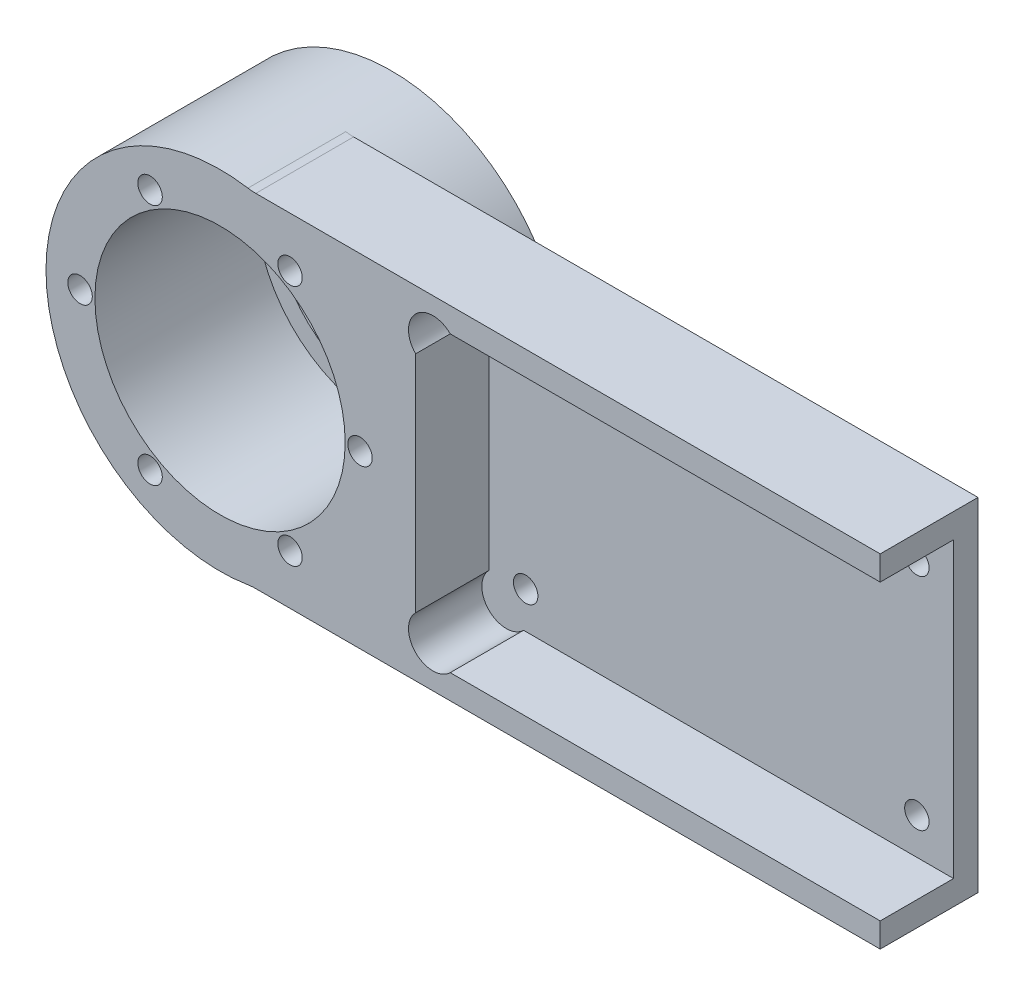
SolidWorks part; units mm, degrees
material "1060 Alloy"
ref_plane "Front Plane" through (0, 0, 0) normal (0, 0, 1) x (1, 0, 0)
ref_plane "Top Plane" through (0, 0, 0) normal (0, 1, 0) x (1, 0, 0)
ref_plane "Right Plane" through (0, 0, 0) normal (1, 0, 0) x (0, 0, -1)
sketch "Sketch1" plane through (0, 0, 0) normal (0, 0, 1) x (1, 0, 0)
  line L0 (8.1998, 44.45) -> (171.45, 44.45)
  line L1 (8.1998, -44.45) -> (171.45, -44.45)
  line L3 (171.45, 44.45) -> (171.45, 38.1)
  line L4 (171.45, -44.45) -> (171.45, -38.1)
  line L5 (171.45, 44.45) -> (171.45, -44.45) construction
  line L6 (171.45, 38.1) -> (50.8, 38.1)
  line L7 (50.8, 38.1) -> (50.8, -38.1)
  line L8 (50.8, -38.1) -> (171.45, -38.1)
  line L9 (171.45, 38.1) -> (171.45, -38.1)
  circle A0 centre (0, 0) radius 32.5
  arc A1 (8.1998, 44.45) -> (8.1998, -44.45) centre (0, 0) ccw
  point P3 (171.45, 0)
  dimension "D1" = 65
  dimension "D4" = 12.7
  dimension "D6" = 50.8
  dimension "D2" = 88.9
  dimension "D3" = 120.65
  dimension "D5" = 6.35
extrude "Boss-Extrude2" add sketch "Sketch1" along normal blind 6.35 contours L0 A1 L1 L4 L8 L7 L6 L3 A0 | L9 L6 L7 L8 region at (37.5693, 0, 0) region at (111.125, 0, 0)
extrude "Boss-Extrude3" add sketch "Sketch1<3>" along normal blind 19.05 from surface contours L0 A1 L1 L4 L8 L7 L6 L3 A0 region at (37.5693, 0, 0) starting at face at (76.475, 0, 6.35)
sketch "Sketch1<3>" plane through (0, 0, 0) normal (0, 0, 1) x (1, 0, 0) same geometry as "Sketch1"
sketch "Sketch2" plane through (0, 0, 6.35) normal (0, 0, 1) x (1, 0, 0)
  line L0 (171.45, -38.1) -> (171.45, 38.1) construction
  line L1 (50.8, -38.1) -> (50.8, 38.1) construction
  line L4 (50.8, 38.1) -> (171.45, 38.1) construction
  line L5 (50.8, 38.1) -> (171.45, 38.1) construction
  line L6 (171.45, -38.1) -> (50.8, -38.1) construction
  line L7 (171.45, -38.1) -> (50.8, -38.1) construction
  circle A0 centre (60.325, 28.575) radius 3.175
  circle A1 centre (161.925, 28.575) radius 3.175
  circle A2 centre (161.925, -28.575) radius 3.175
  circle A3 centre (60.325, -28.575) radius 3.175
  circle A15 centre (0, 0) radius 38.85 construction
  arc A16 (8.1998, 44.45) -> (8.1998, -44.45) centre (0, 0) ccw construction
  dimension "D1" = 6.35
  dimension "D2" = 6.35
  dimension "D4" = 9.525
  dimension "D5" = 9.525
  dimension "D6" = 9.525
  dimension "D3" = 9.525
  dimension "D7" = 9.525
  dimension "D8" = 9.525
extrude "Cut-Extrude1" cut sketch "Sketch2" against normal through all and the other way through all
sketch "Sketch3" plane through (0, 0, 25.4) normal (0, 0, 1) x (1, 0, 0)
  line L0 (50.8, 38.1) -> (59.7803, 29.1197) construction
  line L1 (50.8, 38.1) -> (171.45, 38.1) construction
  line L2 (50.8, 0) -> (32.5, 0) construction
  line L3 (50.8, -38.1) -> (50.8, 38.1) construction
  circle A0 centre (55.2901, 33.6099) radius 6.35
  circle A1 centre (0, 0) radius 32.5 construction
  circle A2 centre (55.2901, -33.6099) radius 6.35
  dimension "D1" = 12.7
  dimension "D2" = 45
extrude "Cut-Extrude2" cut sketch "Sketch3" against normal up to surface (19.05 mm away) up to face at (63.5, -28.575, 6.35)
sketch "Sketch4" plane through (0, 0, 0) normal (0, 0, -1) x (-1, 0, 0)
  line L0 (-31.75, 54.9926) -> (0, 0) construction
  line L1 (0, 0) -> (31.75, 54.9926) construction
  line L2 (-8.1998, -44.45) -> (-171.45, -44.45) construction
  line L3 (0, 0) -> (63.5, 0) construction
  line L4 (0, 0) -> (31.75, -54.9926) construction
  line L9 (-40.7836, 44.45) -> (-8.1998, 44.45)
  line L10 (-8.1998, 44.45) -> (-171.45, 44.45) construction
  line L11 (-8.1998, -44.45) -> (-40.7836, -44.45)
  line L12 (0, 0) -> (-63.5, 0) construction
  line L13 (0, 0) -> (-31.75, -54.9926) construction
  arc A1 (-40.8506, -48.6156) -> (-40.8506, 48.6156) centre (0, 0) ccw construction
  arc A2 (-20.7603, 56.6402) -> (-38.6717, 46.2991) centre (-31.75, 54.9926) ccw
  arc A8 (38.6717, 46.2991) -> (20.7603, 56.6402) centre (31.75, 54.9926) ccw
  arc A9 (59.432, -10.3411) -> (59.432, 10.3411) centre (63.5, 0) ccw
  arc A10 (20.7603, -56.6402) -> (38.6717, -46.2991) centre (31.75, -54.9926) ccw
  arc A11 (-38.6717, -46.2991) -> (-20.7603, -56.6402) centre (-31.75, -54.9926) ccw
  circle A13 centre (-31.75, 54.9926) radius 4.7625
  arc A14 (-38.6717, 46.2991) -> (-40.7836, 44.45) centre (0, 0) ccw
  circle A15 centre (31.75, 54.9926) radius 4.7625
  arc A16 (-8.1998, -44.45) -> (-8.1998, 44.45) centre (0, 0) ccw construction
  arc A17 (20.7603, 56.6402) -> (-20.7603, 56.6402) centre (0, 0) ccw
  circle A18 centre (63.5, 0) radius 4.7625
  circle A19 centre (31.75, -54.9926) radius 4.7625
  arc A20 (59.432, 10.3411) -> (38.6717, 46.2991) centre (0, 0) ccw
  arc A21 (38.6717, -46.2991) -> (59.432, -10.3411) centre (0, 0) ccw
  circle A22 centre (-31.75, -54.9926) radius 4.7625
  arc A23 (-20.7603, -56.6402) -> (20.7603, -56.6402) centre (0, 0) ccw
  arc A24 (-8.1998, -44.45) -> (-8.1998, 44.45) centre (0, 0) ccw
  arc A25 (-40.7836, -44.45) -> (-38.6717, -46.2991) centre (0, 0) ccw
  circle A26 centre (-63.5, 0) radius 4.7625
  point P48 (0, 0)
  dimension "D1" = 6.35
  dimension "D2" = 127
  dimension "D3" = 6
  dimension "D8" = 60.325
  dimension "D9" = 9.525
extrude "Boss-Extrude5" [suppressed] add sketch "Sketch4" against normal blind 6.35
fillet "Fillet1" radius 12.7 2 edges at (8.1998, -44.45, 12.7) (8.1998, 44.45, 12.7)
fillet "Fillet2" [suppressed] radius 12.7
sketch "Sketch5" plane through (0, 0, 0) normal (0, 0, -1) x (-1, 0, 0)
  arc A0 (-7.2516, -44.6145) -> (-7.2516, 44.6145) centre (0, 0) ccw construction
  arc A1 (-7.2516, -44.6145) -> (-7.2516, 44.6145) centre (0, 0) ccw
  circle A6 centre (0, 0) radius 32.5 construction
  circle A11 centre (0, 0) radius 32.5
  arc A12 (-7.2516, 44.6145) -> (-7.2516, -44.6145) centre (0, 0) ccw
  arc A13 (-7.2516, -44.6145) -> (-9.2891, -44.45) centre (-9.2891, -57.15) ccw construction
extrude "Boss-Extrude6" add sketch "Sketch5" along normal blind 19.05
sketch "Sketch6" plane through (0, 0, -19.05) normal (0, 0, -1) x (-1, 0, 0)
  circle A0 centre (0, 0) radius 32.5 construction
  circle A1 centre (0, 0) radius 32.5
  circle A2 centre (0, 0) radius 27.5
  dimension "D1" = 55
extrude "Boss-Extrude7" add sketch "Sketch6" against normal blind 2.54
sketch "Sketch7" plane through (0, 0, -19.05) normal (0, 0, -1) x (-1, 0, 0)
  circle A0 centre (0, 0) radius 67.6783
  dimension "D1" = 135.3566
sketch "Sketch9" plane through (0, 0, -19.05) normal (0, 0, -1) x (-1, 0, 0)
  line L0 (0, 0) -> (36.35, 0) construction
  line L1 (0, 27.5) -> (0, 45.2) construction
  circle A0 centre (0, 0) radius 27.5 construction
  circle A1 centre (0, 0) radius 45.2 construction
  circle A2 centre (0, 0) radius 36.35 construction
  circle A3 centre (36.35, 0) radius 3.175
  circle A4 centre (-60.325, 28.575) radius 3.175 construction
  circle A5 centre (18.175, -31.48) radius 3.175
  circle A6 centre (-18.175, -31.48) radius 3.175
  circle A7 centre (-36.35, 0) radius 3.175
  circle A8 centre (-18.175, 31.48) radius 3.175
  circle A9 centre (18.175, 31.48) radius 3.175
  point P11 (0, 36.35)
  point P27 (0, 0)
  dimension "D1" = 6
extrude "Cut-Extrude3" cut sketch "Sketch9" against normal through all both and the other way through all
